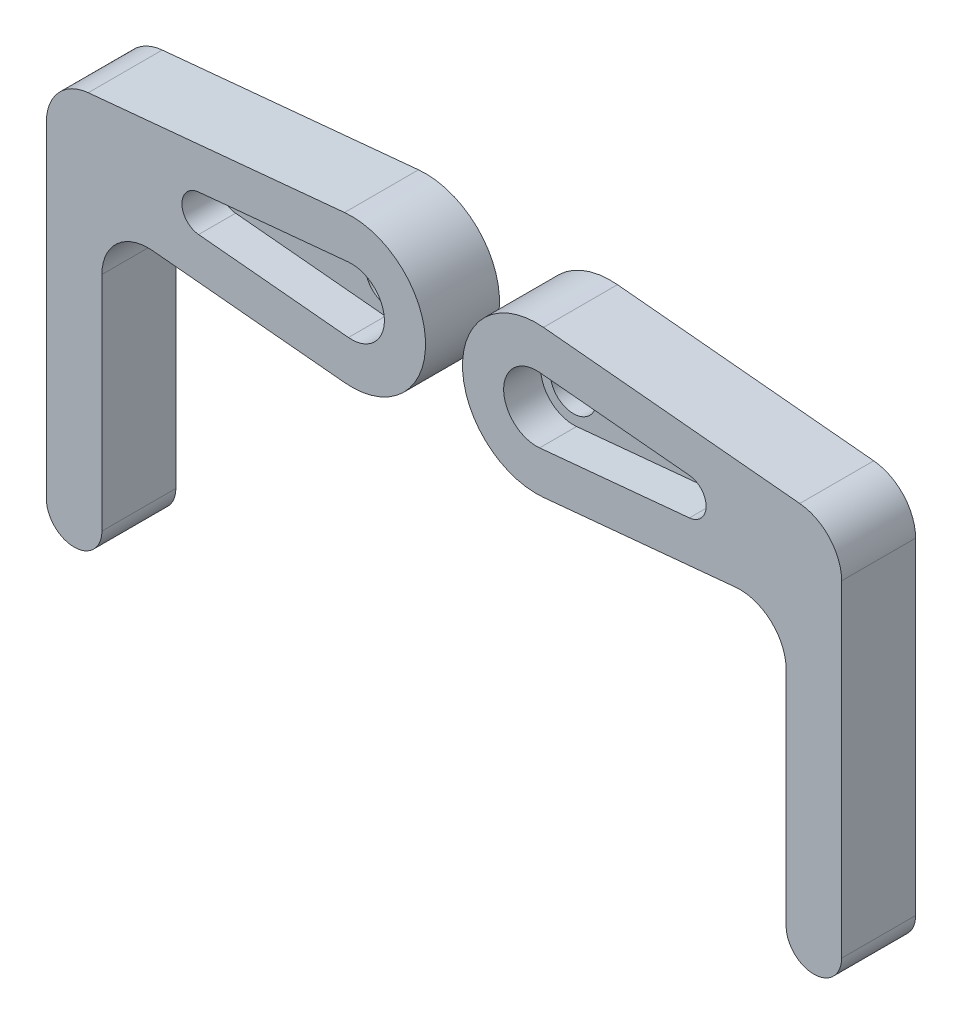
SolidWorks part; units mm, degrees
ref_plane "Front Plane" through (0, 0, 0) normal (0, 0, 1) x (1, 0, 0)
ref_plane "Top Plane" through (0, 0, 0) normal (0, 1, 0) x (1, 0, 0)
ref_plane "Right Plane" through (0, 0, 0) normal (1, 0, 0) x (0, 0, -1)
sketch "Esquisse1" plane through (0, 0, 0) normal (0, 0, 1) x (1, 0, 0)
  line L0 (-3.55, 0) -> (-3.55, 5.3986) construction
  line L1 (0.3365, 3.534) -> (16.5396, 1.991)
  line L2 (16.5396, -1.991) -> (0.3365, -3.534)
  line L3 (18.35, 0) -> (18.35, 4.9554) construction
  line L4 (0.7584, 7.964) -> (33, 4.8936)
  line L5 (0.7584, -7.964) -> (27, -5.465)
  line L6 (27, -5.465) -> (27, -35)
  line L7 (33, -35) -> (33, 4.8936)
  arc A0 (0.3365, 3.534) -> (0.3365, -3.534) centre (0, 0) ccw
  arc A1 (16.5396, -1.991) -> (16.5396, 1.991) centre (16.35, 0) ccw
  arc A2 (33, -35) -> (27, -35) centre (30, -35) cw
  arc A3 (0.7584, -7.964) -> (0.7584, 7.964) centre (0, 0) cw
  dimension "D2" = 3.55
  dimension "D3" = 2
  dimension "D5" = 6
  dimension "D6" = 8
  dimension "D1" = 21.9
  dimension "D4" = 35
  dimension "D7" = 30
extrude "Main" add sketch "Esquisse1" along normal blind 4
sketch "Esquisse2" plane through (0, 0, 0) normal (0, 0, -1) x (-1, 0, 0)
  line L0 (-0.7584, -7.964) -> (-27, -5.465)
  line L2 (-27, -5.465) -> (-27, -35) construction
  line L3 (-0.7584, 7.964) -> (-33, 4.8936)
  line L4 (-33, 4.8936) -> (-33, -35)
  line L5 (-27, -5.465) -> (-27, -35)
  line L6 (-0.7584, -7.964) -> (-27, -5.465) construction
  arc A1 (-27, -35) -> (-33, -35) centre (-30, -35) cw
  circle A2 centre (0, 0) radius 2.5
  arc A3 (-0.7584, -7.964) -> (-0.7584, 7.964) centre (0, 0) ccw
  arc A4 (-33, -35) -> (-27, -35) centre (-30, -35) ccw construction
  dimension "D1" = 5
extrude "OriginalBracket" add sketch "Esquisse2" along normal blind 4
fillet "Fillet1" radius 5 2 edges at (27, -5.465, 0) (33, 4.8936, 0)
ref_plane "Plane1" through (-10, 0, 0) normal (1, 0, 0) x (0, 0, -1)
mirror "Mirror2" about plane through (-10, 0, 0) normal (1, 0, 0) of bodies 102
